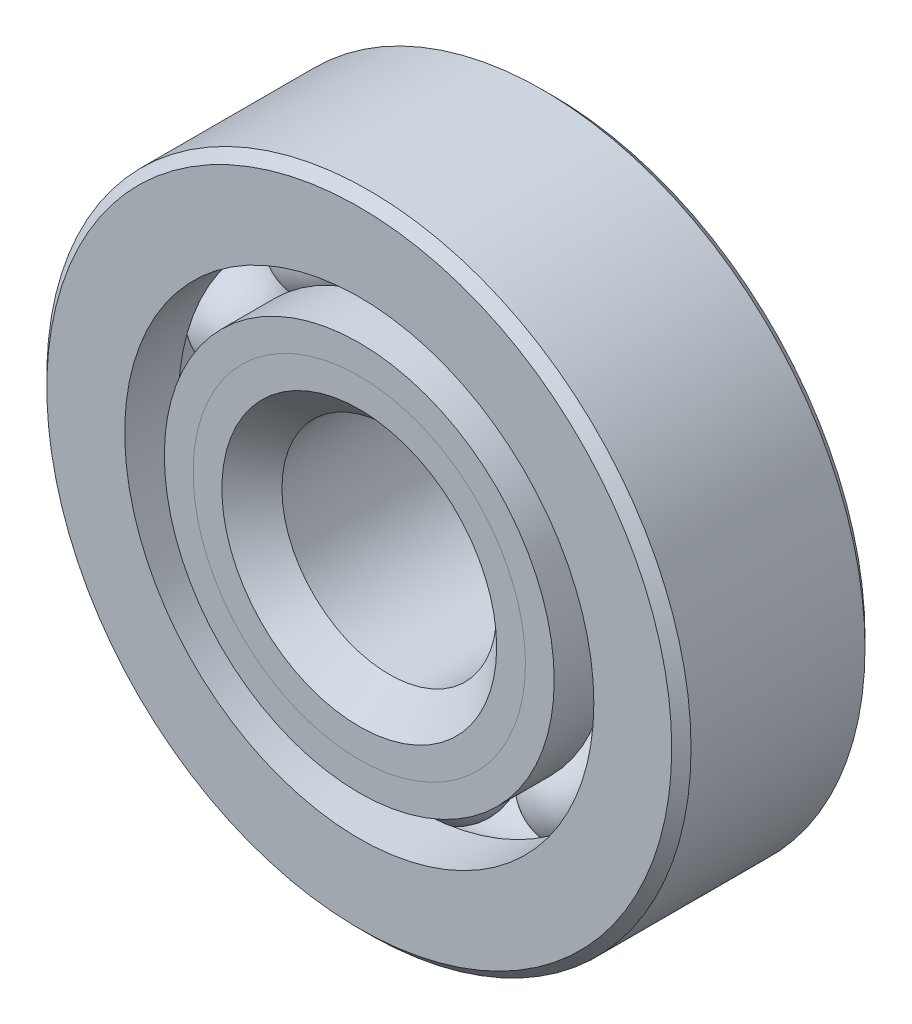
SolidWorks part; units mm, degrees
ref_plane "Front Plane" through (0, 0, 0) normal (0, 0, 1) x (1, 0, 0)
ref_plane "Top Plane" through (0, 0, 0) normal (0, 1, 0) x (1, 0, 0)
ref_plane "Right Plane" through (0, 0, 0) normal (1, 0, 0) x (0, 0, -1)
sketch "Sketch1" plane through (0, 0, 0) normal (1, 0, 0) x (0, 0, -1)
  line L0 (-4.5, 0) -> (4.5, 0) construction
  line L1 (0, 15) -> (0, -15) construction
  line L2 (4.05, 15) -> (-4.05, 15)
  line L3 (-4.05, 15) -> (-4.5, 14.55)
  line L4 (-4.5, 14.55) -> (-4.5, 10.9231)
  line L5 (-4.5, 10.9231) -> (-2, 10.9231)
  line L6 (4.5, 10.9231) -> (2, 10.9231)
  line L7 (4.5, 14.55) -> (4.5, 10.9231)
  line L8 (4.05, 15) -> (4.5, 14.55)
  line L9 (0, 15) -> (0, 10) construction
  line L10 (0, 10) -> (0, 5) construction
  arc A0 (-2, 10.9231) -> (2, 10.9231) centre (0, 10) cw
  point P14 (0, 5)
  dimension "Width" = 9
  dimension "OD" = 30
  dimension "D1" = 45
  dimension "D2" = 0.45
  dimension "D3" = 4
  dimension "D4" = 0.9231
revolve "Revolve1" add sketch "Sketch1" angle 360 about L0
sketch "Sketch2" plane through (0, 0, 0) normal (1, 0, 0) x (0, 0, -1)
  line L0 (-4.5, 9.0769) -> (-2, 9.0769)
  line L1 (-4.5, 14.55) -> (-4.5, -14.55) construction
  line L2 (-4.5, 9.0769) -> (-4.5, 7.7378)
  line L3 (-4.5, 7.7378) -> (-3.1609, 6.3986)
  line L4 (-3.1609, 6.3986) -> (0, 6.3986)
  line L5 (0, 15) -> (0, -15) construction
  line L6 (0, 6.3986) -> (0, 7.7973)
  line L7 (0, 7.7973) -> (0, 5) construction
  line L8 (-4.5, 9.0769) -> (-4.5, 6.3986) construction
  line L9 (-4.5, 6.3986) -> (-3.1609, 6.3986) construction
  arc A0 (-2, 9.0769) -> (0, 7.7973) centre (0, 10) ccw
  arc A1 (2, 10.9231) -> (-2, 10.9231) centre (0, 10) ccw construction
  circle A2 centre (0, 10) radius 2.2027 construction
  dimension "D1" = 45
revolve "Revolve2" add sketch "Sketch2" angle 360 about L0
sketch "Sketch3" plane through (0, 0, 0) normal (1, 0, 0) x (0, 0, -1)
  line L0 (-4.5, 7.7378) -> (-3.1609, 6.3986)
  line L1 (-3.1609, 6.3986) -> (0, 6.3986)
  line L2 (0, 6.3986) -> (0, 7.7973)
  line L3 (-4.5, 7.7378) -> (-4.5, 6.3986)
  line L4 (-4.5, 9.0769) -> (-4.5, 6.3986) construction
  line L5 (-4.5, 6.3986) -> (-3.1014, 5)
  line L6 (-3.1014, 5) -> (4.05, 5)
  line L7 (4.05, 15) -> (4.05, -15) construction
  line L8 (4.05, 5) -> (4.5, 5.45)
  line L9 (4.5, -14.55) -> (4.5, 14.55) construction
  line L10 (4.5, 5.45) -> (4.5, 9.0769)
  line L11 (4.5, 9.0769) -> (2, 9.0769)
  line L13 (4.05, 15) -> (4.5, 14.55) construction
  circle A0 centre (0, 10) radius 2.2027 construction
  arc A1 (2, 9.0769) -> (0, 7.7973) centre (0, 10) cw
revolve "Revolve3" add sketch "Sketch3" angle 360 about L0
sketch "Sketch4" plane through (0, 0, 0) normal (1, 0, 0) x (0, 0, -1)
  line L0 (-2.2027, 10) -> (2.2027, 10)
  circle A1 centre (0, 10) radius 2.2027 construction
  arc A2 (-2.2027, 10) -> (2.2027, 10) centre (0, 10) cw
  arc A3 (2, 10.9231) -> (-2, 10.9231) centre (0, 10) ccw construction
revolve "Revolve4" add sketch "Sketch4" angle 360 about L0
ref_axis "Axis1" through (0, 0, -4.5) along (0, 0, 1)
pattern_circular "CirPattern1" count 10 every 36 about axis through (0, 0, -4.5) along (0, 0, 1) of bodies 104
equation "\"D2@Sketch1\" = \"Width@Sketch1\"*.05"
equation "\"D3@Sketch1\" = \"Width@Sketch1\"/2.25"
equation "\"D4@Sketch1\" = (((\"OD@Sketch1\"-\"Width@Sketch1\")/2)/3.25)/3.5"
equation "\"D2@CirPattern1\" = 360/\"Balls@CirPattern1\""
